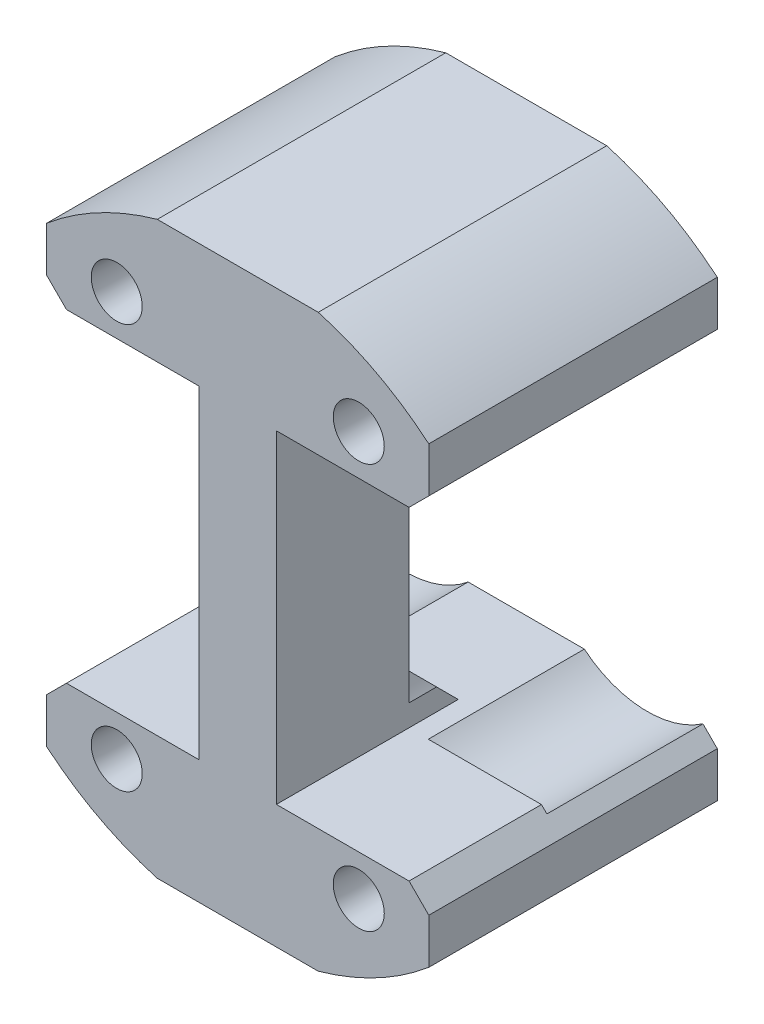
SolidWorks part; units mm, degrees
material "PET"
ref_plane "Front Plane" through (0, 0, 0) normal (0, 0, 1) x (1, 0, 0)
ref_plane "Top Plane" through (0, 0, 0) normal (0, 1, 0) x (1, 0, 0)
ref_plane "Right Plane" through (0, 0, 0) normal (1, 0, 0) x (0, 0, -1)
sketch "Sketch1" plane through (0, 0, 0) normal (0, 0, 1) x (1, 0, 0)
  line L0 (-3.2766, -10) -> (-12.2766, -10) construction
  line L1 (-12.2766, -10.3969) -> (12.2766, -10.3969)
  line L2 (-12.2766, -10.3969) -> (-12.2766, -18.3344)
  line L3 (-12.2766, -18.3344) -> (12.2766, -18.3344)
  line L4 (12.2766, -10.3969) -> (12.2766, -18.3344)
  line L6 (-12.2766, -10) -> (-12.2766, -12.5) construction
  line L8 (12.2766, -12.5) -> (12.2766, -10) construction
  dimension "D1" = 0.3969
  dimension "D2" = 7.9375
extrude "Boss-Extrude1" add sketch "Sketch1" along normal up to surface (18.5375 mm away)
sketch "Sketch8" plane through (0, 0, 0) normal (0, 0, -1) x (-1, 0, 0)
  line L0 (5.1723, -18.3344) -> (12.2766, -18.3344)
  line L4 (12.2766, -18.3344) -> (12.2766, -10.3969)
  line L5 (12.2766, -10.3969) -> (-12.2766, -10.3969)
  line L6 (-12.2766, -10.3969) -> (-12.2766, -18.3344)
  line L7 (-12.2766, -18.3344) -> (12.2766, -18.3344)
  line L8 (12.2766, -18.3344) -> (12.2766, -14.5667)
  line L10 (-12.2766, -14.5667) -> (-12.2766, -18.3344)
  line L11 (-12.2766, -18.3344) -> (-5.1723, -18.3344)
  arc A0 (-17.3537, -7.8581) -> (17.3537, -7.8581) centre (0, 0) ccw construction
  arc A1 (-12.2766, -14.5667) -> (-5.1723, -18.3344) centre (0, 0) ccw
  arc A2 (5.1723, -18.3344) -> (12.2766, -14.5667) centre (0, 0) ccw
  dimension "D1" = 0
extrude "Cut-Extrude2" cut sketch "Sketch8" against normal through all
ref_plane "Plane1" through (0, 0, 0) normal (0, -1, 0) x (-1, 0, 0)
mirror "Mirror2" about plane through (0, 0, 0) normal (0, -1, 0) of bodies 106 102
sketch "Sketch3" plane through (0, 0, 18.5375) normal (0, 0, 1) x (1, 0, 0)
  line L0 (0, 10.3969) -> (0, -10.3969) construction
  line L1 (-12.2766, 10.3969) -> (12.2766, 10.3969) construction
  line L2 (-12.2766, -10.3969) -> (12.2766, -10.3969) construction
  line L3 (-3.2766, 10) -> (-3.2766, -10) construction
  line L4 (2.4829, -10.3969) -> (-2.4829, -10.3969)
  line L5 (2.4829, -10.3969) -> (2.4829, 10.3969)
  line L6 (2.4829, 10.3969) -> (-2.4829, 10.3969)
  line L7 (-2.4829, -10.3969) -> (-2.4829, 10.3969)
  line L8 (2.4829, -10.3969) -> (-2.4829, 10.3969) construction
  line L9 (2.4829, 10.3969) -> (-2.4829, -10.3969) construction
  point P6 (0, 0)
  dimension "D1" = 0.7937
extrude "Boss-Extrude2" add sketch "Sketch3" against normal blind 8.509
chamfer "Chamfer2" distance 3.175 angle 45 2 edges at (0, 10.3969, 10.0285) (0, -10.3969, 10.0285)
chamfer "Chamfer4" distance 1.27 angle 45 4 edges at (-12.2766, -10.3969, 9.2688) (-12.2766, 10.3969, 9.2688) (12.2766, 10.3969, 9.2688) (12.2766, -10.3969, 9.2688)
sketch "Sketch2" plane through (0, 0, 0) normal (0, 0, -1) x (-1, 0, 0)
  line L0 (-28.4114, 0) -> (28.4114, 0) construction
  arc A0 (4.6029, 0) -> (10.9503, 0) centre (7.7766, -5.5) ccw
  arc A1 (-10.9503, 0) -> (-4.6029, 0) centre (-7.7766, -5.5) ccw
  arc A2 (4.6029, 0) -> (10.9503, 0) centre (7.7766, 5.5) cw
  arc A3 (-10.9503, 0) -> (-4.6029, 0) centre (-7.7766, 5.5) cw
  circle A4 centre (7.7766, -5.5) radius 3.175 construction
  dimension "D1" = 12.7
extrude "Cut-Extrude1" cut sketch "Sketch2" against normal up to surface (10.0285 mm away) up to face at (0, 0, 10.0285)
hole_wizard "Hole1" positions "Sketch4" profile "Sketch5" legacy
sketch "Sketch4" plane through (0, 0, 18.5375) normal (0, 0, 1) x (1, 0, 0)
  point P0 (-7.7766, 13)
  point P3 (7.7766, 13)
  point P6 (7.7766, -13)
  point P9 (-7.7766, -13)
sketch "Sketch5" plane through (-7.7766, 13, 18.5375) normal (1, 0, 0) x (0, -1, 0)
  line L0 (0, 0) -> (0, 2.921)
  line L1 (0, 2.921) -> (1.4986, 2.921)
  line L2 (1.4986, 2.921) -> (1.6383, 0)
  line L3 (1.6383, 0) -> (0, 0)
  line L4 (0, 110) -> (0, -10) construction
  dimension "Minor Diameter" = 2.9972
  dimension "Depth" = 2.921
  dimension "Major Diameter" = 3.2766
hole_wizard "#0 Clearance Hole1" positions "Sketch10" profile "Sketch11" hole size "#0" standard "ANSI Inch"
sketch "Sketch10" plane through (0, 0, 18.5375) normal (0, 0, 1) x (1, 0, 0)
  point P0 (7.7766, 13)
  point P3 (7.7766, -13)
  point P6 (-7.7766, -13)
  point P9 (-7.7766, 13)
sketch "Sketch11" plane through (7.7766, 13, 18.5375) normal (1, 0, 0) x (0, -1, 0)
  line L0 (0, 0) -> (0, 6.9071)
  line L1 (0, 6.9071) -> (0.9271, 6.35)
  line L2 (0.9271, 6.35) -> (0.9271, 0)
  line L5 (0.9271, 0) -> (0, 0)
  line L10 (0, 6.9071) -> (-0.9271, 6.35) construction
  line L11 (0, -6.35) -> (0, 107.95) construction
  dimension "Hole Dia." = 1.8542
  dimension "Hole Depth" = 6.35
  dimension "Drill Angle" = 118
hole_wizard "Hole2" positions "3DSketch1" profile "Sketch9" legacy
sketch3d "3DSketch1"
  line L0 (7.435, -11.8408, 0) -> (7.435, -17.5392, 0) construction
  line L2 (-7.7474, -11.8499, 0) -> (-7.7474, -17.4034, 0) construction
  line L4 (0, 0, 0) -> (-12.2766, 0, 0) construction
  line L6 (-12.2766, 11.6669, 0) -> (-12.2766, 14.5667, 0) construction
  line L7 (7.435, 11.8408, 0) -> (7.435, 17.5392, 0) construction
  line L9 (-7.7474, 11.8499, 0) -> (-7.7474, 17.4034, 0) construction
  arc A0 (11.3553, -10.7455, 0) -> (3.7339, -10.3969, 0) centre (7.7766, -5.5, 0) ccw construction
  arc A1 (5.1723, -18.3344, 0) -> (12.2766, -14.5667, 0) centre (0, 0, 0) ccw construction
  arc A2 (-3.7339, -10.3969, 0) -> (-11.3553, -10.7455, 0) centre (-7.7766, -5.5, 0) ccw construction
  arc A3 (-12.2766, -14.5667, 0) -> (-5.1723, -18.3344, 0) centre (0, 0, 0) ccw construction
  arc A4 (3.7339, 10.3969, 0) -> (11.3553, 10.7455, 0) centre (7.7766, 5.5, 0) ccw construction
  arc A5 (5.1723, 18.3344, 0) -> (12.2766, 14.5667, 0) centre (0, 0, 0) ccw construction
  arc A6 (-11.3553, 10.7455, 0) -> (-3.7339, 10.3969, 0) centre (-7.7766, 5.5, 0) ccw construction
  arc A7 (-12.2766, 14.5667, 0) -> (-5.1723, 18.3344, 0) centre (0, 0, 0) ccw construction
  point P4 (7.435, -14.69, 0)
  point P6 (-7.7474, -14.6946, 0)
  point P15 (7.7766, -5.5, -6.35)
  point P19 (0, 0, 19.05)
  point P27 (-7.7766, -5.5, -6.35)
  point P31 (0, 0, 19.05)
  point P44 (7.435, 14.69, 0)
  point P46 (-7.7474, 14.6946, 0)
  point P54 (7.7766, 5.5, -6.35)
  point P58 (0, 0, -19.05)
  point P65 (-7.7766, 5.5, -6.35)
  point P69 (0, 0, -19.05)
  point P72 (7.435, 14.69, 0)
  point P75 (7.435, -14.69, 0)
sketch "Sketch9" plane through (7.435, -14.69, 0) normal (1, 0, 0) x (0, 1, 0)
  line L0 (0, 0) -> (0, 2.921)
  line L1 (0, 2.921) -> (1.4986, 2.921)
  line L2 (1.4986, 2.921) -> (1.6383, 0)
  line L3 (1.6383, 0) -> (0, 0)
  line L4 (0, 110) -> (0, -10) construction
  dimension "Minor Diameter" = 2.9972
  dimension "Depth" = 2.921
  dimension "Major Diameter" = 3.2766
hole_wizard "#0 Clearance Hole2" positions "Sketch12" profile "Sketch13" hole size "#0" standard "ANSI Inch"
sketch "Sketch12" plane through (0, 0, 0) normal (0, 0, -1) x (-1, 0, 0)
  point P0 (-7.435, -14.69)
  point P3 (-7.435, 14.69)
  point P6 (7.7474, 14.6946)
  point P9 (7.7474, -14.6946)
sketch "Sketch13" plane through (7.435, -14.69, 0) normal (1, 0, 0) x (0, 1, 0)
  line L0 (0, 0) -> (0, 6.9071)
  line L1 (0, 6.9071) -> (0.9271, 6.35)
  line L2 (0.9271, 6.35) -> (0.9271, 0)
  line L5 (0.9271, 0) -> (0, 0)
  line L10 (0, 6.9071) -> (-0.9271, 6.35) construction
  line L11 (0, -6.35) -> (0, 107.95) construction
  dimension "Hole Dia." = 1.8542
  dimension "Hole Depth" = 6.35
  dimension "Drill Angle" = 118
